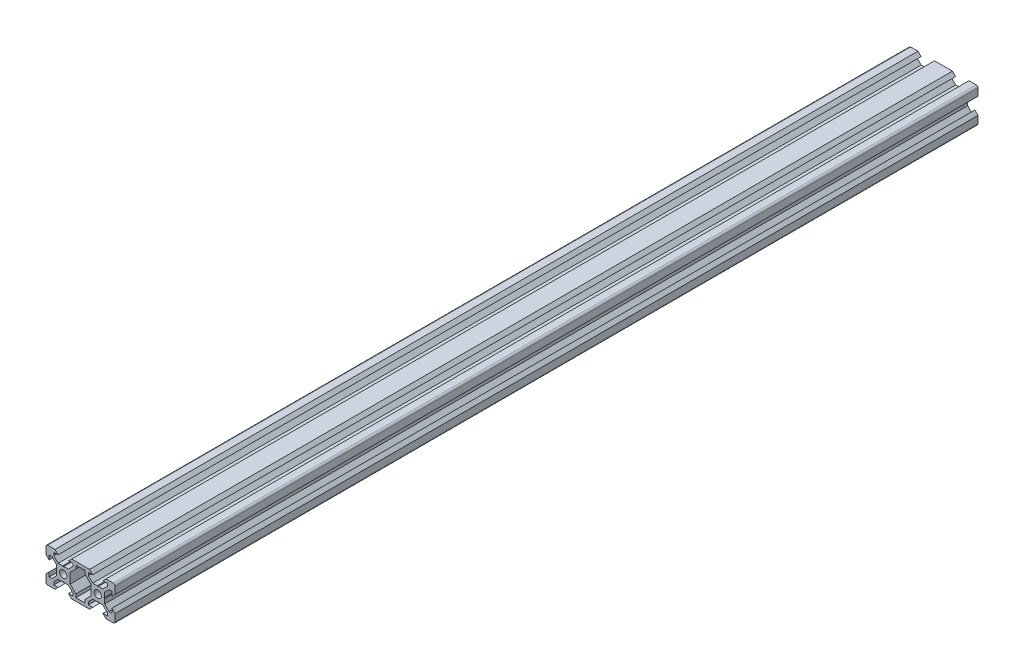
SolidWorks part; units mm, degrees
material "6063-T5"
ref_plane "Plano frontal" through (0, 0, 0) normal (0, 0, 1) x (1, 0, 0)
ref_plane "Plano superior" through (0, 0, 0) normal (0, 1, 0) x (1, 0, 0)
ref_plane "Plano direito" through (0, 0, 0) normal (1, 0, 0) x (0, 0, -1)
sketch "Esboço1" plane through (0, 0, 0) normal (0, 0, 1) x (1, 0, 0)
  line L1 (-19, 10) -> (19, 10)
  line L2 (-20, 9) -> (-20, -9)
  line L3 (-19, -10) -> (19, -10)
  line L4 (20, 9) -> (20, -9)
  line L5 (0, -10) -> (0, 10) construction
  line L6 (-20, 0) -> (20, 0) construction
  arc A0 (-20, -9) -> (-19, -10) centre (-19, -9) ccw
  arc A1 (19, -10) -> (20, -9) centre (19, -9) ccw
  arc A2 (19, 10) -> (20, 9) centre (19, 9) cw
  arc A3 (-19, 10) -> (-20, 9) centre (-19, 9) ccw
  point P0 (0, 0)
  dimension "D3" = 1
  dimension "D1" = 40
  dimension "D2" = 20
extrude "Ressalto-extrusão1" add sketch "Esboço1" along normal blind 500
sketch "Esboço2" plane through (0, 0, 500) normal (0, 0, 1) x (1, 0, 0)
  line L0 (-14.8, 10) -> (-13, 8.2)
  line L1 (19, 10) -> (-19, 10) construction
  line L2 (-14.8, 10) -> (-5.2, 10)
  line L3 (-13, 8.2) -> (-15.5, 8.2)
  line L4 (-15.5, 8.2) -> (-15.5, 6.5607)
  line L5 (-15.5, 6.5607) -> (-12.9393, 4)
  line L6 (-12.9393, 4) -> (-10.3, 4)
  line L7 (-10, 0) -> (-10, 10) construction
  line L8 (-19, 9) -> (-10, 0) construction
  line L9 (-4.5, 6.5607) -> (-7.0607, 4)
  line L10 (-4.5, 8.2) -> (-4.5, 6.5607)
  line L11 (-7, 8.2) -> (-4.5, 8.2)
  line L12 (-5.2, 10) -> (-7, 8.2)
  line L13 (-10.3, 4) -> (-10, 3.7)
  line L14 (-9.7, 4) -> (-10, 3.7)
  line L15 (-9.7, 4) -> (-7.0607, 4)
  line L16 (0, 10) -> (0, 0) construction
  line L17 (0, 0) -> (-10, 0) construction
  line L18 (-2.7, 8.2) -> (-2.7, 6.2393)
  line L19 (-2.7, 6.2393) -> (-6, 2.9393)
  line L20 (-6, 2.9393) -> (-6, 0)
  line L21 (-2.7, 8.2) -> (2.7, 8.2)
  line L22 (-3.4393, 5.5) -> (-6, 2.9393) construction
  line L23 (-2.7, 8.2) -> (-2.7, 6.5607) construction
  line L24 (6, 2.9393) -> (6, 0)
  line L25 (6, 0) -> (-6, 0)
  line L26 (2.7, 6.2393) -> (6, 2.9393)
  line L27 (2.7, 8.2) -> (2.7, 6.2393)
  circle A0 centre (-10, 0) radius 2.1
  point P34 (0, 8.2)
  dimension "D8" = 4.2
  dimension "D1" = 6
  dimension "D2" = 10
  dimension "D3" = 1.8
  dimension "D4" = 45
  dimension "D5" = 6
  dimension "D6" = 11
  dimension "D7" = 1.5
  dimension "D9" = 0.3
  dimension "D10" = 1.8
  dimension "D11" = 1.5
extrude "CANAL" cut sketch "Esboço2" against normal blind 800 contours L9 L15 L14 L13 L6 L5 L4 L3 L0 L2 L12 L11 L10
extrude "FURO" cut sketch "Esboço2<5>" against normal through all contours A0
sketch "Esboço2<5>" plane through (0, 0, 500) normal (0, 0, 1) x (1, 0, 0) same geometry as "Esboço2"
extrude "Corte-extrusão4" cut sketch "Esboço2<6>" against normal through all contours L25 L20 L19 L18 L21 L27 L26 L24
sketch "Esboço2<6>" plane through (0, 0, 500) normal (0, 0, 1) x (1, 0, 0) same geometry as "Esboço2"
pattern_circular "PadrãoCircular2" count 3 over 180 about axis through (-10, 0, 0) along (0, 0, 1) of "CANAL"
mirror "Espelhar2" about plane through (0, 0, 0) normal (1, 0, 0) of "Corte-extrusão4", "FURO", "PadrãoCircular2", "CANAL"
mirror "Espelhar3" about plane through (0, 0, 0) normal (0, 1, 0) of "Corte-extrusão4"
